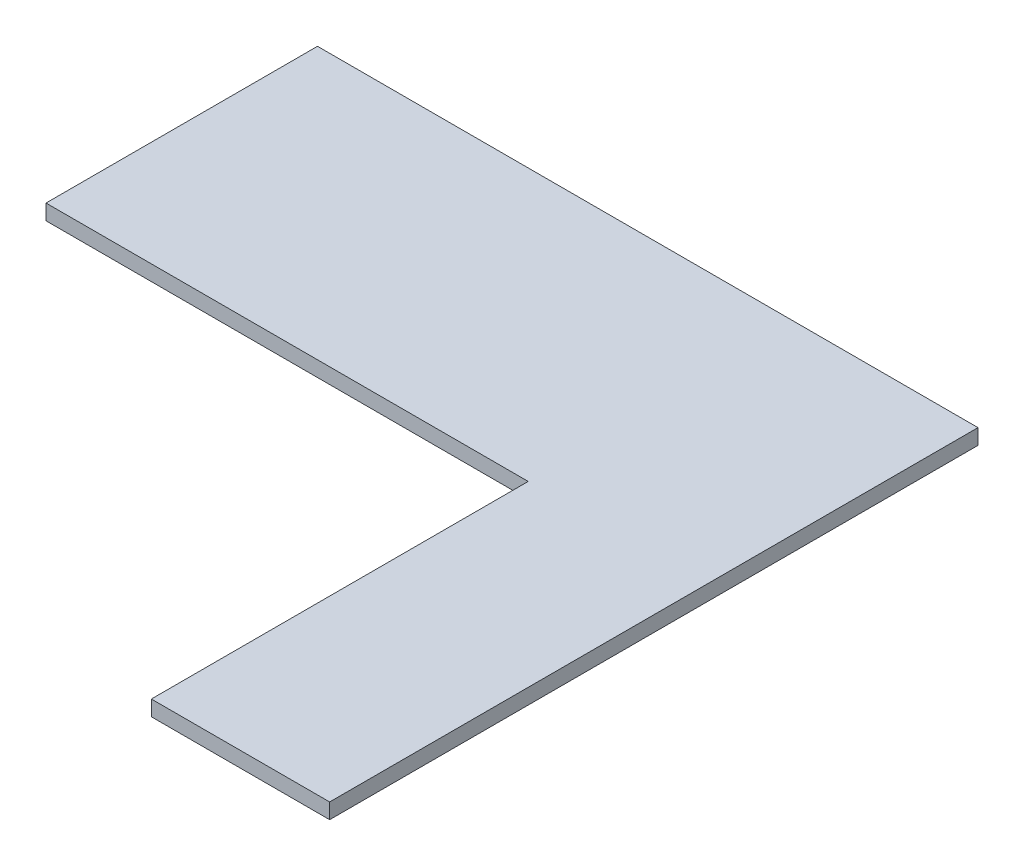
SolidWorks part; units mm, degrees
ref_plane "Спереди" through (0, 0, 0) normal (0, 0, 1) x (1, 0, 0)
ref_plane "Сверху" through (0, 0, 0) normal (0, 1, 0) x (1, 0, 0)
ref_plane "Справа" through (0, 0, 0) normal (1, 0, 0) x (0, 0, -1)
sketch "Эскиз1" plane through (0, 0, 0) normal (0, 1, 0) x (1, 0, 0)
  line L0 (0, 0) -> (0, 670)
  line L1 (0, 670) -> (1630, 670)
  line L2 (1630, 670) -> (1630, -930)
  line L3 (1630, -930) -> (1190, -930)
  line L4 (1190, -930) -> (1190, 0)
  line L5 (1190, 0) -> (0, 0)
extrude "Бобышка-Вытянуть1" add sketch "Эскиз1" along normal blind 38
